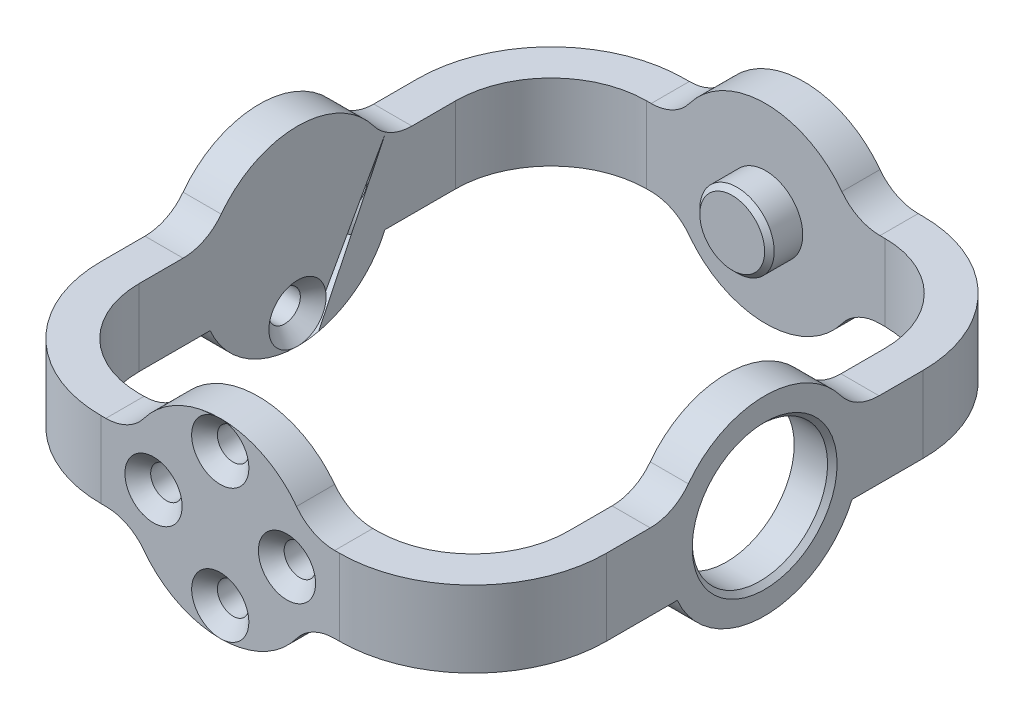
SolidWorks part; units mm, degrees
ref_plane "Front Plane" through (0, 0, 0) normal (0, 0, 1) x (1, 0, 0)
ref_plane "Top Plane" through (0, 0, 0) normal (0, 1, 0) x (1, 0, 0)
ref_plane "Right Plane" through (0, 0, 0) normal (1, 0, 0) x (0, 0, -1)
ref_plane "Plane1" through (0, 0, 26.6) normal (0, 0, 1) x (1, 0, 0)
sketch "Sketch1" plane through (0, 0, 26.6) normal (0, 0, 1) x (1, 0, 0)
  circle A0 centre (0, 0) radius 10
  dimension "D1" = 20
ref_plane "Plane2" through (0, 0, -26.6) normal (0, 0, 1) x (1, 0, 0)
sketch "Sketch2" plane through (0, 0, -26.6) normal (0, 0, 1) x (1, 0, 0)
  circle A0 centre (0, 0) radius 10
  dimension "D1" = 20
sketch "Sketch3" plane through (0, 0, 0) normal (0, 0, 1) x (1, 0, 0)
  line L0 (0, 0) -> (-67.3223, 0)
  line L1 (-17.5, -30) -> (17.5, -30)
  line L2 (-17.5, -30) -> (-17.5, 30)
  line L3 (-17.5, 30) -> (17.5, 30)
  line L4 (17.5, -30) -> (17.5, 30)
  line L5 (-17.5, -30) -> (17.5, 30) construction
  line L6 (-17.5, 30) -> (17.5, -30) construction
  line L7 (0, 0) -> (-14.678, -31.4771)
  line L8 (28.5389, 19.7934) -> (3.1818, -34.5851)
  line L9 (28.5389, 19.7934) -> (-3.1818, 34.5851)
  line L10 (3.1818, -34.5851) -> (-28.5389, -19.7934)
  line L11 (-3.1818, 34.5851) -> (-28.5389, -19.7934)
  line L12 (28.5389, 19.7934) -> (-28.5389, -19.7934) construction
  line L13 (3.1818, -34.5851) -> (-3.1818, 34.5851) construction
  line L14 (-22.107, 0) -> (-22.107, -6)
  arc A0 (17.5, -30) -> (-34.7311, 0) centre (0, 0) cw
  point P0 (0, 0)
  dimension "D1" = 60
  dimension "D2" = 35
  dimension "D3" = 65
  dimension "D4" = 35
  dimension "D5" = 25
  dimension "D6" = 60
  dimension "D7" = 6
sketch "Sketch4" plane through (0, 0, 0) normal (0, 1, 0) x (1, 0, 0)
  line L0 (-38.1239, 26.6) -> (38.1239, 26.6) construction
  line L1 (22.5, -26.6) -> (-22.5, -26.6)
  line L2 (22.5, -26.6) -> (22.5, 26.6)
  line L3 (22.5, 26.6) -> (-22.5, 26.6)
  line L4 (-22.5, -26.6) -> (-22.5, 26.6)
  line L5 (22.5, -26.6) -> (-22.5, 26.6) construction
  line L6 (22.5, 26.6) -> (-22.5, -26.6) construction
  line L7 (26.5, -30.6) -> (26.5, 30.6)
  line L8 (26.5, 30.6) -> (-26.5, 30.6)
  line L9 (-26.5, -30.6) -> (-26.5, 30.6)
  line L10 (26.5, -30.6) -> (-26.5, -30.6)
  point P0 (0, 0)
  dimension "D1" = 45
  dimension "D2" = 4
extrude "Boss-Extrude1" add sketch "Sketch4" along normal blind 4 and the other way blind 4
sketch "Sketch5" plane through (0, 0, 30.6) normal (0, 0, 1) x (1, 0, 0)
  circle A0 centre (0, 0) radius 10
extrude "Boss-Extrude2" add sketch "Sketch5" against normal blind 4
sketch "Sketch6" plane through (0, 0, -30.6) normal (0, 0, -1) x (-1, 0, 0)
  circle A0 centre (0, 0) radius 10
extrude "Boss-Extrude3" add sketch "Sketch6" against normal blind 4
sketch "Sketch7" plane through (0, 0, 30.6) normal (0, 0, 1) x (1, 0, 0)
  circle A0 centre (0, 0) radius 7 construction
  circle A1 centre (0, 7) radius 1.65
  circle A2 centre (7, 0) radius 1.65
  circle A3 centre (0, -7) radius 1.65
  circle A4 centre (-7, 0) radius 1.65
  point P14 (0, 0)
  dimension "D1" = 14
  dimension "D2" = 3.3
  dimension "D3" = 4
extrude "Cut-Extrude1" cut sketch "Sketch7" against normal blind 4
chamfer "Chamfer1" distance 1.35 angle 45 4 edges at (1.65, -7, 30.6) (8.65, 0, 30.6) (-5.35, 0, 30.6) (1.65, 7, 30.6)
sketch "Sketch8" plane through (0, 0, -26.6) normal (0, 0, 1) x (1, 0, 0)
  circle A0 centre (0, 0) radius 3.9
  dimension "D1" = 7.8
extrude "Boss-Extrude4" add sketch "Sketch8" along normal blind 3.5
fillet "Fillet1" radius 10 4 edges at (-22.5, 0, 26.6) (-22.5, 0, -26.6) (22.5, 0, 26.6) (22.5, 0, -26.6)
fillet "Fillet2" radius 14 4 edges at (-26.5, 0, 30.6) (26.5, 0, 30.6) (-26.5, 0, -30.6) (26.5, 0, -30.6)
fillet "Fillet3" radius 5 8 edges at (9.1652, -4, -28.6) (-9.1652, -4, -28.6) (-9.1652, 4, -28.6) (9.1652, 4, -28.6) (-9.1652, -4, 28.6) (9.1652, -4, 28.6) (-9.1652, 4, 28.6) (9.1652, 4, 28.6)
chamfer "Chamfer2" distance 0.5 angle 45 1 edges at (3.9, 0, -23.1)
sketch "Sketch9" plane through (-26.5, 0, 0) normal (-1, 0, 0) x (0, 0, 1)
  circle A0 centre (0, 0) radius 10
  dimension "D1" = 20
extrude "Boss-Extrude5" add sketch "Sketch9" against normal blind 4
sketch "Sketch10" plane through (26.5, 0, 0) normal (1, 0, 0) x (0, 0, -1)
  circle A0 centre (0, 0) radius 10
extrude "Boss-Extrude6" add sketch "Sketch10" against normal blind 4
sketch "Sketch11" plane through (26.5, 0, 0) normal (1, 0, 0) x (0, 0, -1)
  circle A0 centre (0, 0) radius 7.1
  dimension "D1" = 14.2
extrude "Cut-Extrude2" cut sketch "Sketch11" against normal blind 4
sketch "Sketch12" plane through (-26.5, 0, 0) normal (-1, 0, 0) x (0, 0, 1)
  circle A0 centre (0, 0) radius 7 construction
  circle A1 centre (0, 7) radius 1.65
  circle A2 centre (7, 0) radius 1.65
  circle A3 centre (0, -7) radius 1.65
  circle A4 centre (-7, 0) radius 1.65
  point P13 (0, 0)
  dimension "D1" = 14
  dimension "D2" = 3.3
  dimension "D3" = 4
extrude "Cut-Extrude3" cut sketch "Sketch12" against normal blind 4
chamfer "Chamfer3" distance 1.35 angle 45 4 edges at (-22.5, -7, 1.65) (-22.5, 0, 8.65) (-22.5, 0, -5.35) (-22.5, 7, 1.65)
fillet "Fillet4" radius 5 4 edges at (24.5, 4, -9.1652) (-24.5, 4, -9.1652) (24.5, 4, 9.1652) (-24.5, 4, 9.1652)
chamfer "Chamfer4" distance 0.5 angle 45 1 edges at (26.5, 0, -7.1)
